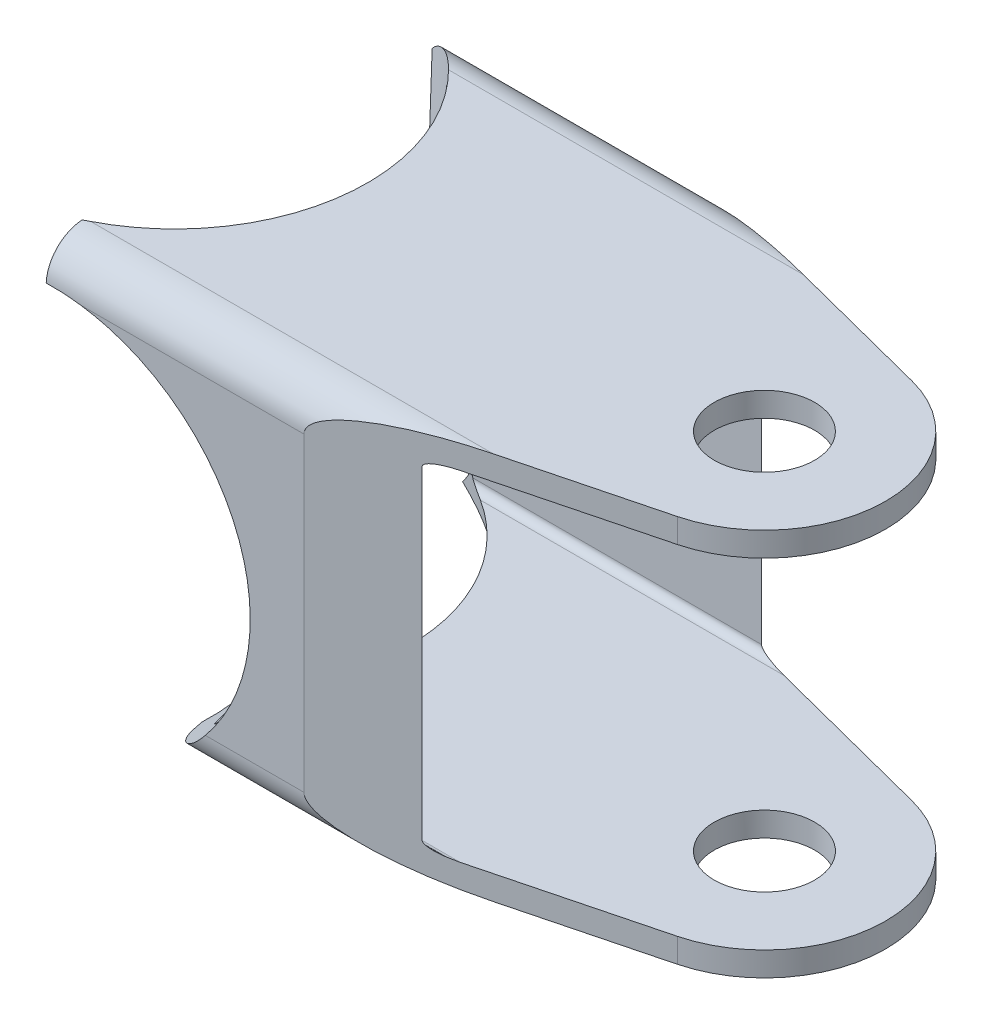
SolidWorks part; units mm, degrees
note: '?' marks a value the reader was unsure of.
ref_plane "Front Plane" through (0, 0, 0) normal (0, 0, 1) x (1, 0, 0)
ref_plane "Top Plane" through (0, 0, 0) normal (0, 1, 0) x (1, 0, 0)
ref_plane "Right Plane" through (0, 0, 0) normal (1, 0, 0) x (0, 0, -1)
sketch "Sketch1" plane through (0, 0, 0) normal (1, 0, 0) x (0, 0, -1)
  line L1 (-10.16, 12.7) -> (10.16, 12.7)
  line L2 (-12.7, 10.16) -> (-12.7, -10.16)
  line L3 (-10.16, -12.7) -> (10.16, -12.7)
  line L4 (12.7, 10.16) -> (12.7, -10.16)
  arc A0 (-10.16, 12.7) -> (-12.7, 10.16) centre (-10.16, 10.16) ccw
  arc A1 (-10.16, -12.7) -> (-12.7, -10.16) centre (-10.16, -10.16) cw
  arc A2 (10.16, 12.7) -> (12.7, 10.16) centre (10.16, 10.16) cw
  arc A3 (12.7, -10.16) -> (10.16, -12.7) centre (10.16, -10.16) cw
  point P4 (0, -12.7)
  point P7 (0, 0)
  point P15 (12.7, 0)
  dimension "D3" = 2.54
  dimension "D4" = 2.54
  dimension "D5" = 2.54
  dimension "D6" = 2.54
  dimension "D1" = 25.4
  dimension "D2" = 20.32
extrude "Boss-Extrude1" add sketch "Sketch1" along normal blind 25.4 and the other way blind 34.925
sketch "Sketch11" plane through (25.4, 0, 0) normal (1, 0, 0) x (0, 0, -1)
  line L0 (-10.16, -12.7) -> (10.16, -12.7) construction
  line L1 (-10.6045, 11.1125) -> (10.6045, 11.1125)
  line L2 (-11.1125, 10.6045) -> (-11.1125, -10.6045)
  line L3 (-10.6045, -11.1125) -> (10.6045, -11.1125)
  line L4 (11.1125, 10.6045) -> (11.1125, -10.6045)
  line L5 (10.16, 12.7) -> (-10.16, 12.7) construction
  line L6 (12.7, -10.16) -> (12.7, 10.16) construction
  line L7 (-12.7, 10.16) -> (-12.7, -10.16) construction
  arc A0 (10.6045, 11.1125) -> (11.1125, 10.6045) centre (10.6045, 10.6045) cw
  arc A1 (10.6045, -11.1125) -> (11.1125, -10.6045) centre (10.6045, -10.6045) ccw
  arc A2 (-11.1125, -10.6045) -> (-10.6045, -11.1125) centre (-10.6045, -10.6045) ccw
  arc A3 (-10.6045, 11.1125) -> (-11.1125, 10.6045) centre (-10.6045, 10.6045) ccw
  dimension "D1" = 1.5875
  dimension "D2" = 1.5875
  dimension "D3" = 1.5875
  dimension "D4" = 1.5875
  dimension "D5" = 0.508
extrude "Cut-Extrude4" cut sketch "Sketch11" against normal through all
sketch "Sketch12" plane through (0, 12.7, 0) normal (0, 1, 0) x (1, 0, 0)
  line L1 (0, 12.7) -> (50.8, 12.7)
  line L2 (50.8, 12.7) -> (50.8, -12.7)
  line L12 (50.8, -12.7) -> (0, -12.7)
  line L13 (19.4444, -7.6861) -> (0, -12.7)
  line L14 (19.4444, 7.6861) -> (0, 12.7)
  line L15 (-34.925, -12.7) -> (25.4, -12.7) construction
  line L16 (-34.925, 12.7) -> (25.4, 12.7) construction
  line L18 (25.4, 10.16) -> (25.4, -10.16) construction
  arc A1 (19.4444, -7.6861) -> (19.4444, 7.6861) centre (17.4625, 0) ccw
  point P8 (18.1688, 9.2165)
  dimension "D2" = 50.8
  dimension "D1" = 17.4625
extrude "Cut-Extrude5" cut sketch "Sketch12" against normal through all
sketch "Sketch14" plane through (0, 12.7, 0) normal (0, 1, 0) x (1, 0, 0)
  circle A0 centre (17.4625, 0) radius 3.2893
  arc A2 (19.4444, -7.6861) -> (19.4444, 7.6861) centre (17.4625, 0) ccw construction
  point P0 (17.4625, 0)
  point P6 (25.4, 0)
  dimension "D2" = 6.5786
  dimension "D1" = 7.9375
  dimension "D3" = 17.4625
extrude "Cut-Extrude6" cut sketch "Sketch14" against normal through all
ref_axis "Axis1" through (-31.7972, -6.5052, -32.7402) along (0.3107, 0.0843, 0.9468)?
ref_axis "Axis2" through (-26.7678, 67.1366, -5.1321) along (0.0803, -0.9941, 0.0722)?
ref_axis "Axis3" through (83.5932, 24.9849, 0.004) along (-0.9647, -0.2634, 0)?
ref_axis "Axis4" through (-37.4632, 56.5065, 0.0415) along (0.2634, -0.9647, -0.0006)?
ref_point "Point2"
ref_point "Point6"
ref_point "Point8"
ref_point "Point10"
ref_plane "Plane1" through (-21.0532, -3.5917, 0) normal (0.3107, 0.0843, 0.9468) x (0.9505, -0.0275, -0.3095)
ref_plane "Plane2" through (-21.3421, 0, -0.2568) normal (0.0803, -0.9941, 0.0722) x (-0.9968, -0.0801, 0.0058)
ref_plane "Plane3" through (-22.0325, 0, 0.0063) normal (0.2634, -0.9647, -0.0006) x (-0.9647, -0.2634, -0.0002)
ref_plane "Plane4" through (0, 2.1575, 0.004) normal (-0.9647, -0.2634, 0) x (0, 0, 1)
sketch "Sketch16" plane through (-21.0532, -3.5917, 0) normal (0.3107, 0.0843, 0.9468) x (0.9505, -0.0275, -0.3095)
  circle A0 centre (0, 0) radius 12.7
  dimension "D1" = 25.4
sketch "Sketch18" plane through (-22.0325, 0, 0.0063) normal (0.2634, -0.9647, -0.0006) x (-0.9647, -0.2634, -0.0002)
  line L0 (-12.0219, 4.0943) -> (12.0247, -4.0862) construction
  circle A0 centre (0.0014, 0.004) radius 12.7
  dimension "D1" = 25.4
sketch "Sketch19" plane through (0, 2.1575, 0.004) normal (-0.9647, -0.2634, 0) x (0, 0, 1)
  circle A0 centre (0, 0) radius 12.7
  dimension "D1" = 25.4
sketch "Sketch20" plane through (-21.3421, 0, -0.2568) normal (0.0803, -0.9941, 0.0722) x (-0.9968, -0.0801, 0.0058)
  circle A0 centre (0, 0) radius 12.7
  dimension "D1" = 25.4
extrude "Cut-Extrude7" cut sketch "Sketch18" along normal through all
extrude "Cut-Extrude8" cut sketch "Sketch16" along normal through all both and the other way through all
extrude "Cut-Extrude9" cut sketch "Sketch20" against normal through all
ref_plane "Plane5" through (-22.0525, -3.8646, 0.004) normal (-0.9647, -0.2634, 0) x (0, 0, 1)
ref_point "Point12"
sketch "Sketch22" plane through (-22.0525, -3.8646, 0.004) normal (-0.9647, -0.2634, 0) x (0, 0, 1)
  circle A0 centre (0, 0) radius 12.7
  dimension "D1" = 25.4
extrude "Cut-Extrude10" cut sketch "Sketch22" along normal through all
ref_plane "Plane6" through (0, 0, 12.7) normal (0, 0, 1) x (1, 0, 0)
ref_point "Point14"
sketch "Sketch23" plane through (0, 0, 12.7) normal (0, 0, 1) x (1, 0, 0)
  line L0 (-16.8855, -24.8884) -> (-16.8855, 19.9654) construction
  line L2 (-16.8855, -15.755) -> (-16.8855, 16.2591)
  line L3 (-16.8855, -15.755) -> (-42.3779, -15.755)
  line L4 (-16.8855, 16.2591) -> (-42.3779, 16.2591)
  line L5 (-42.3779, -15.755) -> (-42.3779, 16.2591)
  point P4 (-16.8855, -2.4615)
extrude "Cut-Extrude11" cut sketch "Sketch23" against normal through all
